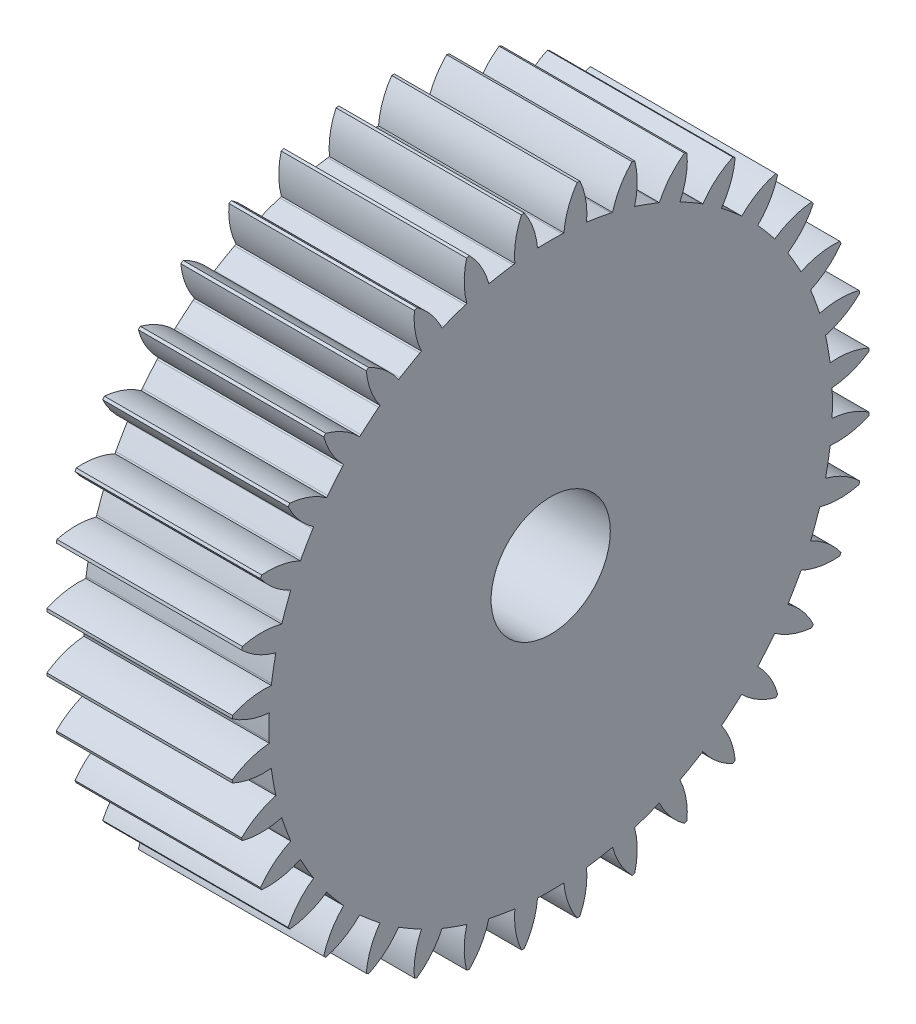
SolidWorks part; units mm, degrees
ref_plane "Front Plane" through (0, 0, 0) normal (0, 0, 1) x (1, 0, 0)
ref_plane "Top Plane" through (0, 0, 0) normal (0, 1, 0) x (1, 0, 0)
ref_plane "Right Plane" through (0, 0, 0) normal (1, 0, 0) x (0, 0, -1)
sketch "Sketch1" plane through (0, 0, 0) normal (1, 0, 0) x (0, 0, -1)
  circle A0 centre (0, 0) radius 120.65
  dimension "D1" = 241.3
extrude "Boss-Extrude1" add sketch "Sketch1" along normal mid plane 70
sketch "Sketch6" plane through (35, 0, 0) normal (1, 0, 0) x (0, 0, -1)
  circle A0 centre (0, 0) radius 22.5
  dimension "D1" = 45
extrude "Cut-Extrude4" cut sketch "Sketch6" against normal through all
sketch "Sketch7" plane through (35, 0, 0) normal (1, 0, 0) x (0, 0, -1)
  line L0 (0, 0) -> (0, 212.7675) construction
  line L1 (0, 106.3837) -> (-4.985, 106.2481)
  line L2 (0, 106.3837) -> (4.985, 106.2481)
  line L3 (-9.975, 120.2369) -> (0, 134.345)
  line L4 (9.975, 120.2369) -> (0, 134.345)
  circle A0 centre (0, 0) radius 106.365 construction
  circle A1 centre (0, 0) radius 114.3 construction
  arc A2 (-4.985, 106.2481) -> (-9.975, 120.2369) centre (-33.8327, 103.8422) ccw
  circle A3 centre (0, 0) radius 120.65 construction
  arc A4 (4.985, 106.2481) -> (9.975, 120.2369) centre (33.8327, 103.8422) cw
  point P12 (0, 134.345)
  point P16 (0, 106.365)
  point P17 (0, 106.365)
  point P18 (0, 106.365)
  point P19 (0, 106.3837)
  dimension "D1" = 228.6
  dimension "D2" = 212.73
  dimension "D3" = 4.99
  dimension "D4" = 19.95
extrude "Cut-Extrude5" cut sketch "Sketch7" against normal through all
fillet "Fillet1" radius 160 1 edges at (0, 106.3837, 0)
pattern_circular "CirPattern1" count 36 over 360 about axis through (35, 0, 0) along (1, 0, 0) of "Fillet1", "Cut-Extrude5"
